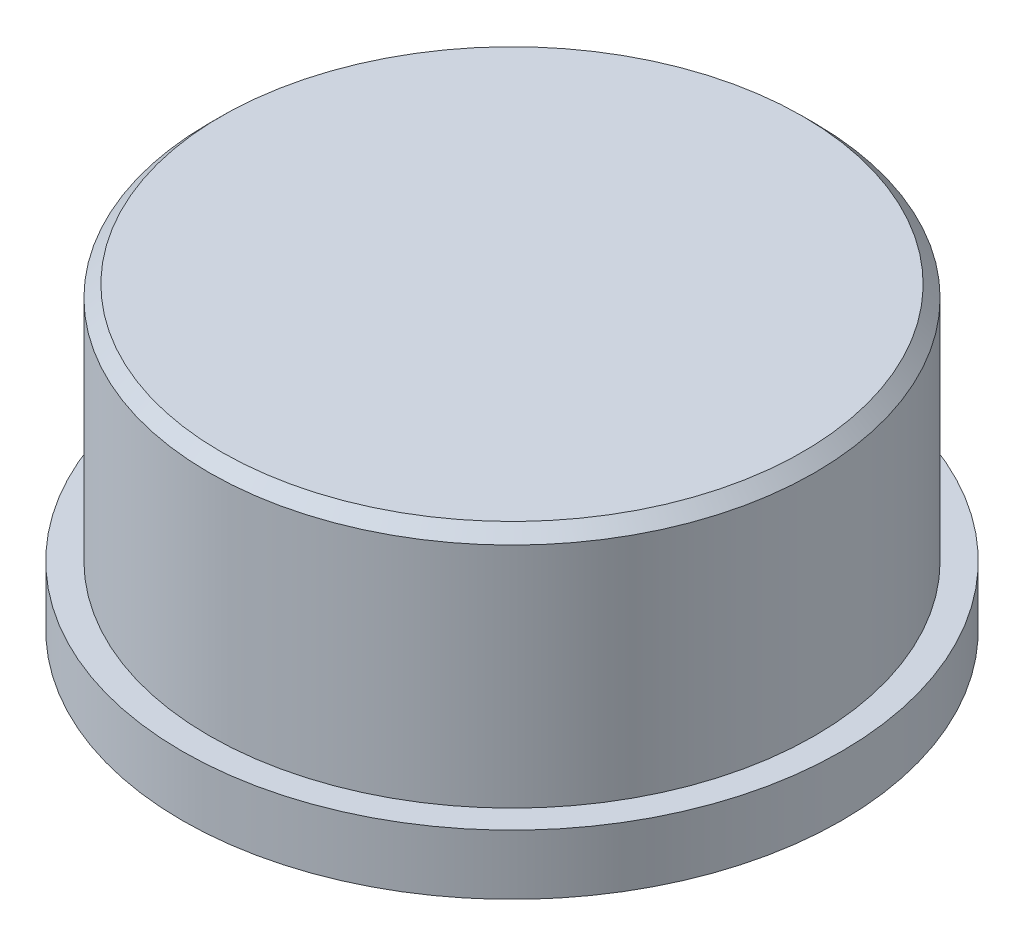
SolidWorks part; units mm, degrees
material "ABS"
ref_plane "Front Plane" through (0, 0, 0) normal (0, 0, 1) x (1, 0, 0)
ref_plane "Top Plane" through (0, 0, 0) normal (0, 1, 0) x (1, 0, 0)
ref_plane "Right Plane" through (0, 0, 0) normal (1, 0, 0) x (0, 0, -1)
sketch "Sketch1" plane through (0, 0, 0) normal (0, 1, 0) x (1, 0, 0)
  circle A0 centre (0, 0) radius 5.5
  dimension "D1" = 11
extrude "Boss-Extrude1" add sketch "Sketch1" along normal blind 1
sketch "Sketch2" plane through (0, 1, 0) normal (0, 1, 0) x (1, 0, 0)
  circle A0 centre (0, 0) radius 5.05
  dimension "D1" = 10.1
extrude "Boss-Extrude2" add sketch "Sketch2" along normal blind 4
sketch "Sketch3" plane through (0, 0, 0) normal (0, -1, 0) x (1, 0, 0)
  line L1 (3.0022, 0) -> (1.5011, 2.6)
  line L2 (1.5011, 2.6) -> (-1.5011, 2.6)
  line L3 (-1.5011, 2.6) -> (-3.0022, 0)
  line L4 (-3.0022, 0) -> (-1.5011, -2.6)
  line L5 (-1.5011, -2.6) -> (1.5011, -2.6)
  line L6 (1.5011, -2.6) -> (3.0022, 0)
  circle A0 centre (0, 0) radius 2.6 construction
  dimension "D1" = 5.2
extrude "Cut-Extrude1" cut sketch "Sketch3" against normal blind 4 contours L1 L2 L3 L4 L5 L6
chamfer "Chamfer1" distance 0.2 angle 45 1 edges at (0, 5, 5.05)
